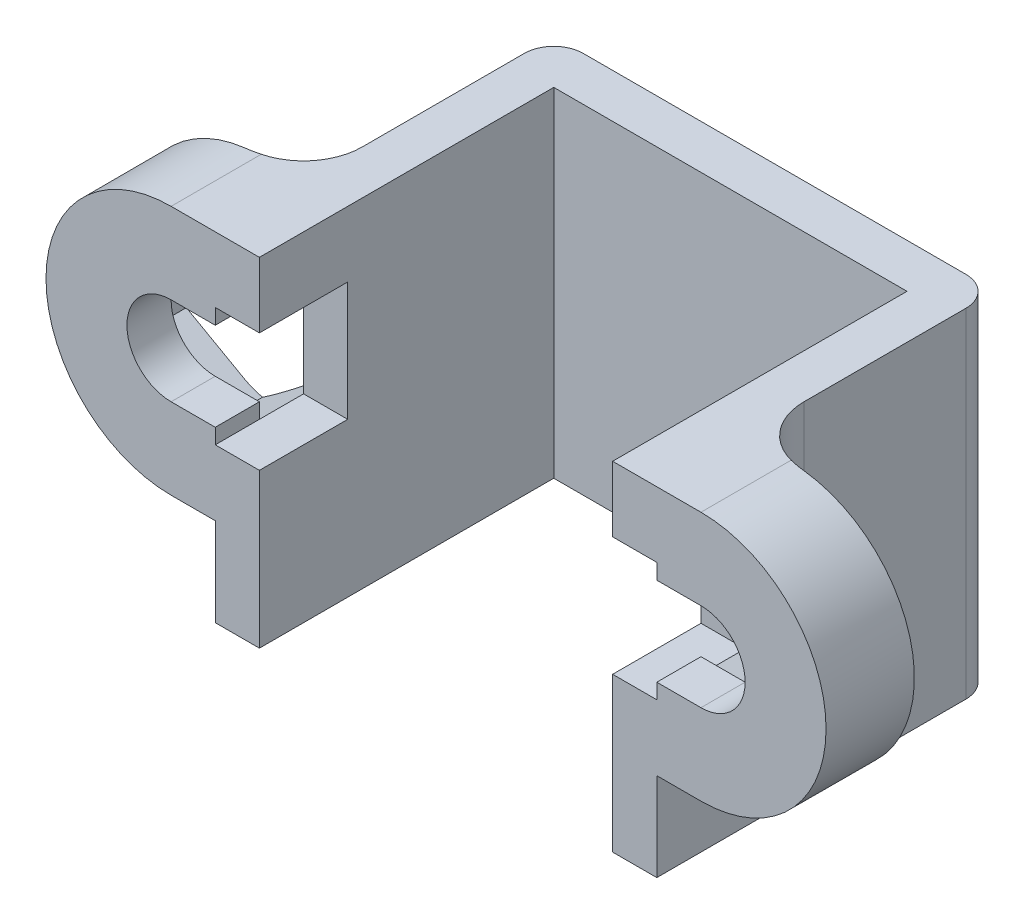
SolidWorks part; units mm, degrees
material "PE High Density"
ref_plane "Front Plane" through (0, 0, 0) normal (0, 0, 1) x (1, 0, 0)
ref_plane "Top Plane" through (0, 0, 0) normal (0, 1, 0) x (1, 0, 0)
ref_plane "Right Plane" through (0, 0, 0) normal (1, 0, 0) x (0, 0, -1)
sketch "Sketch1" plane through (0, 0, 0) normal (0, 1, 0) x (1, 0, 0)
  line L0 (0, 0) -> (0, 11.5)
  line L1 (0, 11.5) -> (-15, 11.5)
  line L2 (-15, 11.5) -> (-15, 0)
  line L3 (-13.5, 0) -> (-13.5, 10)
  line L4 (-13.5, 10) -> (-1.5, 10)
  line L5 (-1.5, 10) -> (-1.5, 0)
  line L6 (-1.5, 0) -> (0, 0)
  line L7 (-13.5, 0) -> (-15, 0)
extrude "Boss-Extrude1" add sketch "Sketch1" along normal blind 11.5
fillet "Fillet4" radius 1 2 edges at (0, 5.75, -11.5) (-15, 5.75, -11.5)
sketch "Sketch3" plane through (0, 0, 0) normal (0, 0, 1) x (1, 0, 0)
  line L0 (0, 11.5) -> (1.5, 11.5)
  line L1 (-15, 8.75) -> (-15, 11.5)
  line L2 (0, 11.5) -> (0, 0) construction
  line L3 (0, 3) -> (1.5, 3)
  line L7 (-15, 3) -> (-16.5, 3)
  line L8 (-15, 11.5) -> (-16.5, 11.5)
  line L9 (1.5, 8.75) -> (0, 8.75)
  line L10 (1.5, 5.75) -> (0, 5.75)
  line L11 (-16.5, 8.75) -> (-15, 8.75)
  line L12 (-15, 11.5) -> (-15, 0) construction
  line L13 (-16.5, 5.75) -> (-15, 5.75)
  line L14 (0, 11.5) -> (0, 8.75)
  line L15 (0, 3) -> (0, 5.75)
  line L16 (-15, 5.75) -> (-15, 3)
  arc A0 (1.5, 11.5) -> (1.5, 3) centre (1.5, 7.25) cw
  arc A1 (-16.5, 11.5) -> (-16.5, 3) centre (-16.5, 7.25) ccw
  arc A2 (1.5, 5.75) -> (1.5, 8.75) centre (1.5, 7.25) ccw
  arc A3 (-16.5, 8.75) -> (-16.5, 5.75) centre (-16.5, 7.25) ccw
extrude "Boss-Extrude2" add sketch "Sketch3" against normal blind 3
fillet "Fillet5" radius 2 4 edges at (0, 4.375, -3) (0, 10.125, -3) (-15, 10.125, -3) (-15, 4.375, -3)
sketch "Sketch4" plane through (0, 0, -3) normal (0, 0, -1) x (-1, 0, 0)
  line L1 (15.0002, 5.2329) -> (16.4658, 4.3635)
  line L2 (16.4658, 4.3635) -> (18.9827, 5.7771)
  line L3 (18.9827, 5.7771) -> (19.0169, 8.6637)
  line L4 (19.0169, 8.6637) -> (16.5342, 10.1365)
  line L5 (16.5342, 10.1365) -> (15.0002, 9.275)
  line L7 (15.0002, 9.275) -> (15.0002, 5.2329)
  line L9 (14.0173, 8.7229) -> (13.9831, 5.8363) [skipped]
  line L11 (-3.9827, 5.7771) -> (-4.0169, 8.6637)
  line L12 (-4.0169, 8.6637) -> (-1.5342, 10.1365)
  line L13 (-1.5342, 10.1365) -> (-0.0002, 9.275)
  line L14 (-0.0002, 9.275) -> (-0.0002, 5.2329)
  line L15 (-0.0002, 5.2329) -> (-1.4658, 4.3635)
  line L16 (-1.4658, 4.3635) -> (-3.9827, 5.7771)
extrude "Cut-Extrude1" cut sketch "Sketch4" against normal mid plane 3
sketch "Sketch5" plane through (0, 0, 0) normal (0, 0, 1) x (1, 0, 0)
  line L4 (0.0002, 9.275) -> (0.0002, 5.2329)
  line L5 (0.0002, 5.2329) -> (-1.5, 5.2329)
  line L6 (-1.5, 11.5) -> (-1.5, 0) construction
  line L7 (-13.5, 9.275) -> (-15.0002, 9.275)
  line L8 (-1.5, 9.275) -> (0.0002, 9.275)
  line L9 (-1.5, 5.2329) -> (-1.5, 9.275)
  line L10 (-15.0002, 9.275) -> (-15.0002, 5.2329)
  line L11 (-15.0002, 5.2329) -> (-13.5, 5.2329)
  line L12 (-13.5, 5.2329) -> (-13.5, 9.275)
extrude "Cut-Extrude2" cut sketch "Sketch5" against normal blind 3
